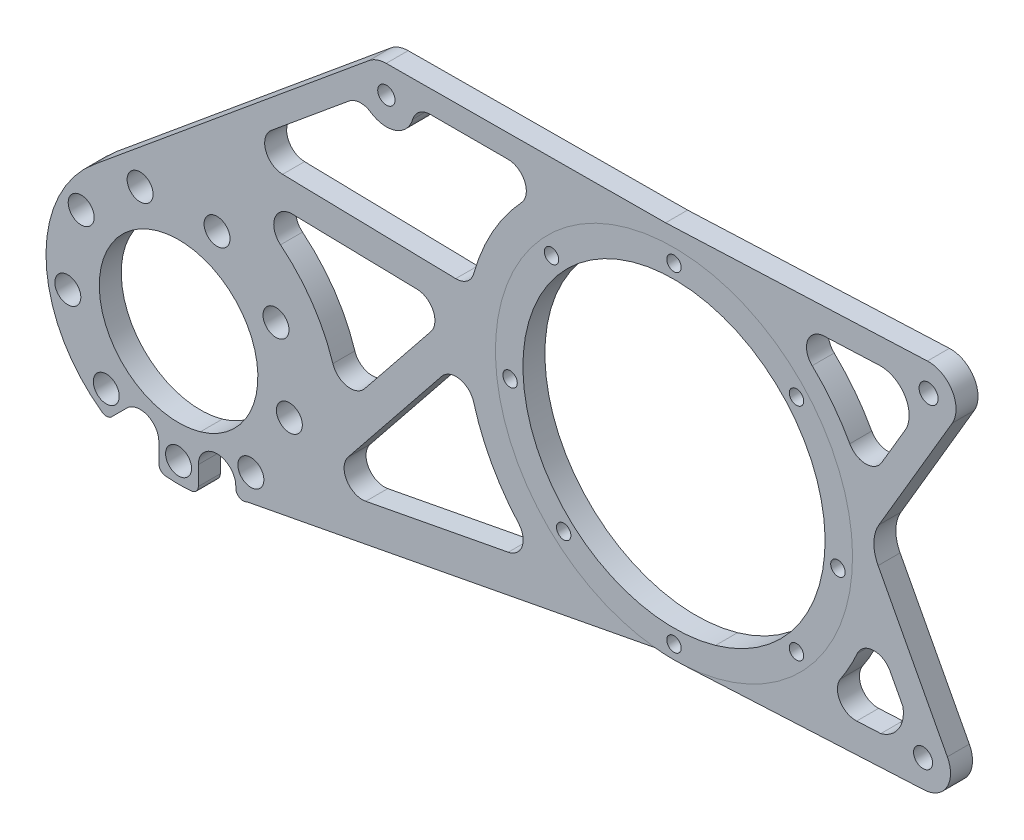
SolidWorks part; units mm, degrees
note: '?' marks a value the reader was unsure of.
material "6061-T6 (SS)"
ref_plane "X-Y Datum" through (0, 0, 0) normal (0, 0, 1) x (1, 0, 0)
ref_plane "X-Z Datum" through (0, 0, 0) normal (0, 1, 0) x (1, 0, 0)
ref_plane "Y-Z Datum" through (0, 0, 0) normal (1, 0, 0) x (0, 0, -1)
sketch "Sketch15" plane through (0, 0, 0) normal (0, 0, 1) x (-1, 0, 0)
  line L0 (-666.75, 77.9015) -> (-548.64, 0) construction
  line L1 (-666.75, 77.9015) -> (-494.9785, 127) construction
  line L8 (-471.7786, 164.3167) -> (-477.0435, 159.0518)
  line L9 (-488.1397, 163.648) -> (-488.1397, 170.2207)
  line L10 (-501.8173, 170.2207) -> (-501.8173, 163.648)
  line L11 (-514.8173, 163.648) -> (-514.8173, 164.225)
  line L17 (-660.4, 0) -> (-548.64, 0)
  line L18 (-777.24, 0) -> (-660.4, 0)
  line L19 (-777.24, 145.034) -> (-777.24, 0)
  line L20 (-789.94, 132.334) -> (-764.54, 157.734)
  line L21 (-789.94, 157.734) -> (-764.54, 132.334)
  line L22 (-789.94, 132.334) -> (-764.54, 132.334)
  line L23 (-789.94, 157.734) -> (-764.54, 157.734)
  line L24 (-789.94, 157.734) -> (-789.94, 132.334)
  line L25 (-764.54, 157.734) -> (-764.54, 132.334)
  line L26 (-543.2372, -4.4272) -> (-459.4185, 97.8608)
  line L27 (-777.24, -6.985) -> (-548.64, -6.985)
  line L28 (-784.225, 0) -> (-784.225, 145.034)
  line L29 (-776.4928, 151.9789) -> (-660.1268, 139.4587)
  line L30 (-660.1268, 139.4587) -> (-518.666, 166.4019)
  circle A0 centre (-567.0211, 20.1088) radius 3 construction
  circle A1 centre (-666.75, 77.9015) radius 52.3875
  circle A2 centre (-777.24, 0) radius 12.7 construction
  circle A4 centre (-548.64, 0) radius 12.7
  circle A6 centre (-777.24, 0) radius 12.7
  circle A7 centre (-753.11, 125.984) radius 3.3 construction
  circle A8 centre (-755.0278, 15.6608) radius 3.3 construction
  circle A9 centre (-567.0211, 20.1088) radius 3 construction
  circle A10 centre (-753.11, 125.984) radius 3.3 construction
  circle A11 centre (-755.0278, 15.6608) radius 3.3 construction
  circle A12 centre (-777.24, 145.034) radius 12.7 construction
  arc A16 (-518.666, 166.4019) -> (-468.5208, 164.5979) centre (-494.9785, 127) ccw
  arc A17 (-468.5208, 164.5979) -> (-471.7786, 164.3167) centre (-469.9826, 162.5207) ccw
  arc A18 (-488.1397, 163.648) -> (-477.0435, 159.0518) centre (-481.6397, 163.648) ccw
  arc A19 (-488.1397, 170.2207) -> (-490.4283, 172.7483) centre (-490.6797, 170.2207) ccw
  arc A20 (-490.4283, 172.7483) -> (-499.5287, 172.7483) centre (-494.9785, 127) ccw
  arc A21 (-499.5287, 172.7483) -> (-501.8173, 170.2207) centre (-499.2773, 170.2207) ccw
  arc A22 (-514.8173, 163.648) -> (-501.8173, 163.648) centre (-508.3173, 163.648) ccw
  arc A23 (-514.8173, 164.225) -> (-518.666, 166.4019) centre (-517.3573, 164.225) ccw
  circle A30 centre (-709.2207, 116.1423) radius 2.5
  circle A31 centre (-624.2793, 39.6607) radius 2.5
  circle A33 centre (-709.2207, 39.6607) radius 2.5
  circle A34 centre (-723.5869, 83.8753) radius 2.5
  circle A35 centre (-609.9131, 83.8753) radius 2.5
  circle A36 centre (-666.75, 20.7515) radius 2.5
  arc A40 (-666.75, 132.5515) -> (-666.75, 137.5515) centre (-666.75, 135.0515) ccw
  arc A41 (-666.75, 137.5515) -> (-666.75, 132.5515) centre (-666.75, 135.0515) ccw
  circle A43 centre (-628.5092, 120.3722) radius 2.5
  circle A45 centre (-666.75, 77.9015) radius 61.9125
  circle A46 centre (-548.64, 0) radius 3.3
  circle A47 centre (-777.24, 0) radius 3.3
  circle A48 centre (-777.24, 145.034) radius 3.3
  circle A49 centre (-548.64, 0) radius 6.985
  circle A50 centre (-777.24, 0) radius 6.985
  circle A51 centre (-777.24, 145.034) radius 6.985
  circle A61 centre (-461.2035, 107.5) radius 4.5
  circle A62 centre (-481.6397, 90.352) radius 4.5
  circle A63 centre (-508.3173, 90.352) radius 4.5
  circle A64 centre (-528.7535, 107.5) radius 4.5
  circle A65 centre (-533.386, 133.7723) radius 4.5
  circle A66 centre (-520.0472, 156.8757) radius 4.5
  circle A67 centre (-494.9785, 166) radius 4.5
  circle A68 centre (-469.9098, 156.8757) radius 4.5
  circle A69 centre (-456.571, 133.7723) radius 4.5
  circle A71 centre (-494.9785, 127) radius 27.4955
  dimension "D2" = 6.6
  dimension "D3" = 6.6
  dimension "D4" = 6.6
  dimension "D5" = 13.97
  dimension "D6" = 13.97
  dimension "D7" = 13.97
  dimension "D1" = 141.4871
extrude "Boss-Extrude1" add sketch "Sketch15" along normal blind 7.62
ref_point "Point1"
ref_point "Point2"
ref_plane "Plane1" through (666.75, -77.9015, 0) normal (-0.9615, -0.2748, 0) x (0, 0, 1)
ref_plane "Plane2" through (494.9785, -127, 0) normal (0.9615, 0.2748, 0) x (0, 0, -1)
split line "Split Line1"
split line "Split Line2"
sketch "Sketch17" plane through (0, 0, 7.62) normal (0, 0, 1) x (1, 0, 0)
  circle A0 centre (666.75, -77.9015) radius 61.9125 construction
  circle A1 centre (666.75, -77.9015) radius 61.9125
split line "Split Line3"
ref_axis "Axis4" through (666.75, -77.9015, 7.62) along (0, 0, -1)?
ref_axis "Axis5" through (494.9785, -127, 7.62) along (0, 0, -1)?
sketch "Sketch18" plane through (0, 0, 7.62) normal (0, 0, 1) x (1, 0, 0)
  line L0 (734.2162, -69.8493) -> (666.75, -77.9015) construction
  line L1 (666.75, -77.9015) -> (753.11, -125.984) construction
  line L2 (663.8529, -10.0183) -> (566.9655, -10.584)
  line L3 (560.9502, -12.7692) -> (465.6763, -91.5741)
  line L4 (514.8173, -163.648) -> (514.8173, -164.225)
  line L5 (501.8173, -170.2207) -> (501.8173, -163.648)
  line L6 (488.1397, -163.648) -> (488.1397, -170.2207)
  line L7 (471.7786, -164.3167) -> (477.0435, -159.0518)
  line L8 (514.8173, -163.648) -> (514.8173, -164.225)
  line L9 (501.8173, -170.2207) -> (501.8173, -163.648)
  line L10 (488.1397, -163.648) -> (488.1397, -170.2207)
  line L11 (471.7786, -164.3167) -> (477.0435, -159.0518)
  line L12 (734.2162, -69.8493) -> (763.2387, -20.4886)
  line L13 (734.2162, -69.8493) -> (761.5313, -121.5334)
  line L14 (754.6217, -6.1445) -> (663.8529, -10.0183)
  line L16 (753.5916, -135.4968) -> (669.8804, -139.7348)
  line L20 (660.1268, -139.4587) -> (518.666, -166.4019) construction
  line L21 (660.1268, -139.4587) -> (518.666, -166.4019)
  circle A0 centre (666.75, -77.9015) radius 67.945 construction
  circle A1 centre (666.75, -77.9015) radius 52.3875
  circle A2 centre (666.75, -77.9015) radius 52.3875
  arc A3 (761.5313, -121.5334) -> (753.5916, -135.4968) centre (753.11, -125.984) cw
  arc A5 (754.6217, -6.1445) -> (763.2387, -20.4886) centre (755.0278, -15.6608) cw
  circle A7 centre (666.75, -77.9015) radius 61.9125 construction
  arc A8 (566.9655, -10.584) -> (560.9502, -12.7692) centre (567.0211, -20.1088) ccw
  arc A9 (669.8804, -139.7348) -> (660.1268, -139.4587) centre (666.75, -77.9015) cw
  arc A10 (514.8173, -164.225) -> (518.666, -166.4019) centre (517.3573, -164.225) ccw
  arc A11 (514.8173, -163.648) -> (501.8173, -163.648) centre (508.3173, -163.648) ccw
  arc A12 (499.5287, -172.7483) -> (501.8173, -170.2207) centre (499.2773, -170.2207) ccw
  arc A13 (490.4283, -172.7483) -> (499.5287, -172.7483) centre (494.9785, -127) ccw
  arc A14 (488.1397, -170.2207) -> (490.4283, -172.7483) centre (490.6797, -170.2207) ccw
  arc A15 (488.1397, -163.648) -> (477.0435, -159.0518) centre (481.6397, -163.648) ccw
  arc A16 (468.5208, -164.5979) -> (471.7786, -164.3167) centre (469.9826, -162.5207) ccw
  arc A17 (518.666, -166.4019) -> (468.5208, -164.5979) centre (494.9785, -127) ccw
  arc A18 (514.8173, -164.225) -> (518.666, -166.4019) centre (517.3573, -164.225) ccw
  arc A19 (514.8173, -163.648) -> (501.8173, -163.648) centre (508.3173, -163.648) ccw
  arc A20 (499.5287, -172.7483) -> (501.8173, -170.2207) centre (499.2773, -170.2207) ccw
  arc A21 (490.4283, -172.7483) -> (499.5287, -172.7483) centre (494.9785, -127) ccw
  arc A22 (488.1397, -170.2207) -> (490.4283, -172.7483) centre (490.6797, -170.2207) ccw
  arc A23 (488.1397, -163.648) -> (477.0435, -159.0518) centre (481.6397, -163.648) ccw
  arc A24 (468.5208, -164.5979) -> (471.7786, -164.3167) centre (469.9826, -162.5207) ccw
  arc A25 (518.666, -166.4019) -> (468.5208, -164.5979) centre (494.9785, -127) ccw
  circle A29 centre (567.0211, -20.1088) radius 3 construction
  circle A30 centre (753.11, -125.984) radius 3.3 construction
  circle A31 centre (755.0278, -15.6608) radius 3.3 construction
  circle A32 centre (567.0211, -20.1088) radius 3
  circle A33 centre (753.11, -125.984) radius 3.3
  circle A34 centre (755.0278, -15.6608) radius 3.3
  circle A35 centre (753.11, -125.984) radius 9.525 construction
  circle A36 centre (755.0278, -15.6608) radius 9.525 construction
  circle A37 centre (567.0211, -20.1088) radius 9.525 construction
  dimension "D5" = 135.89
  dimension "D6" = 19.05
  dimension "D7" = 35.914
  dimension "D1" = 0
  dimension "D2" = 0
extrude "Profile" cut sketch "Sketch18" against normal through all
fillet "Prof Fillet" radius 12.7 1 edges at (734.2162, -69.8493, 3.81)
sketch "Sketch19" plane through (0, 0, 7.62) normal (0, 0, 1) x (1, 0, 0)
  line L0 (732.4887, -55.2476) -> (756.1667, -14.9766) construction
  line L1 (756.1667, -14.9766) -> (700.9038, -17.3351) construction
  line L2 (754.6217, -6.1445) -> (663.8529, -10.0183) construction
  line L3 (737.8071, -63.7419) -> (763.2387, -20.4886) construction
  line L4 (514.8173, -163.648) -> (514.8173, -164.225)
  line L5 (501.8173, -170.2207) -> (501.8173, -163.648)
  line L6 (488.1397, -163.648) -> (488.1397, -170.2207)
  line L7 (471.7786, -164.3167) -> (477.0435, -159.0518)
  line L8 (514.8173, -163.648) -> (514.8173, -164.225)
  line L9 (501.8173, -170.2207) -> (501.8173, -163.648)
  line L10 (488.1397, -163.648) -> (488.1397, -170.2207)
  line L11 (471.7786, -164.3167) -> (477.0435, -159.0518)
  line L12 (734.7219, -92.5501) -> (752.0832, -125.4002) construction
  line L13 (752.0832, -125.4002) -> (715.7448, -127.2398) construction
  line L14 (737.5266, -76.1131) -> (761.5313, -121.5334) construction
  line L15 (746.1204, -114.1176) -> (734.7219, -92.5501)
  line L16 (738.4628, -126.0897) -> (715.7448, -127.2398)
  line L17 (732.4887, -55.2476) -> (747.1519, -30.3088)
  line L18 (753.5916, -135.4968) -> (669.8804, -139.7348) construction
  line L19 (737.5266, -76.1131) -> (761.5313, -121.5334) construction
  line L20 (737.9147, -15.7556) -> (700.9038, -17.3351)
  arc A0 (700.9038, -17.3351) -> (732.4887, -55.2476) centre (666.75, -77.9015) cw construction
  circle A1 centre (666.75, -77.9015) radius 52.3875
  circle A2 centre (666.75, -77.9015) radius 52.3875
  circle A3 centre (548.64, 0) radius 12.7
  circle A4 centre (548.64, 0) radius 12.7
  arc A5 (715.7448, -127.2398) -> (734.7219, -92.5501) centre (666.75, -77.9015) ccw
  circle A7 centre (666.75, -77.9015) radius 61.9125 construction
  arc A8 (715.7448, -127.2398) -> (734.7219, -92.5501) centre (666.75, -77.9015) ccw construction
  arc A10 (514.8173, -164.225) -> (518.666, -166.4019) centre (517.3573, -164.225) ccw
  arc A11 (514.8173, -163.648) -> (501.8173, -163.648) centre (508.3173, -163.648) ccw
  arc A12 (499.5287, -172.7483) -> (501.8173, -170.2207) centre (499.2773, -170.2207) ccw
  arc A13 (490.4283, -172.7483) -> (499.5287, -172.7483) centre (494.9785, -127) ccw
  arc A14 (488.1397, -170.2207) -> (490.4283, -172.7483) centre (490.6797, -170.2207) ccw
  arc A15 (488.1397, -163.648) -> (477.0435, -159.0518) centre (481.6397, -163.648) ccw
  arc A16 (468.5208, -164.5979) -> (471.7786, -164.3167) centre (469.9826, -162.5207) ccw
  arc A17 (518.666, -166.4019) -> (468.5208, -164.5979) centre (494.9785, -127) ccw
  arc A18 (514.8173, -164.225) -> (518.666, -166.4019) centre (517.3573, -164.225) ccw
  arc A19 (514.8173, -163.648) -> (501.8173, -163.648) centre (508.3173, -163.648) ccw
  arc A20 (499.5287, -172.7483) -> (501.8173, -170.2207) centre (499.2773, -170.2207) ccw
  arc A21 (490.4283, -172.7483) -> (499.5287, -172.7483) centre (494.9785, -127) ccw
  arc A22 (488.1397, -170.2207) -> (490.4283, -172.7483) centre (490.6797, -170.2207) ccw
  arc A23 (488.1397, -163.648) -> (477.0435, -159.0518) centre (481.6397, -163.648) ccw
  arc A24 (468.5208, -164.5979) -> (471.7786, -164.3167) centre (469.9826, -162.5207) ccw
  arc A25 (518.666, -166.4019) -> (468.5208, -164.5979) centre (494.9785, -127) ccw
  circle A26 centre (753.11, -125.984) radius 3.3 construction
  circle A27 centre (753.11, -125.984) radius 3.3 construction
  circle A28 centre (753.11, -125.984) radius 9.525 construction
  arc A29 (746.1204, -114.1176) -> (738.4628, -126.0897) centre (735.8004, -115.9518) cw
  circle A30 centre (755.0278, -15.6608) radius 3.3 construction
  circle A31 centre (755.0278, -15.6608) radius 3.3 construction
  circle A32 centre (755.0278, -15.6608) radius 9.525 construction
  arc A33 (737.9147, -15.7556) -> (747.1519, -30.3088) centre (738.3388, -25.6945) cw
  arc A34 (732.4887, -55.2476) -> (700.9038, -17.3351) centre (666.75, -77.9015) ccw
  dimension "D7" = 7.62
  dimension "D8" = 7.62
  dimension "D10" = 19.05
  dimension "D11" = 10.4817
  dimension "D13" = 19.05
  dimension "D14" = 16.689
  dimension "D5" = 8.89
  dimension "D6" = 8.89
  dimension "D9" = 10.16
  dimension "D4" = 10.16
  dimension "D12" = 17.3096
  dimension "D1" = 0
  dimension "D2" = 0
  dimension "D3" = 0
extrude "Cut-Extrude2" cut sketch "Sketch19" against normal through all
fillet "Fillet2" radius 6.35 4 edges at (700.9038, -17.3351, 3.81) (732.4887, -55.2476, 3.81) (734.7219, -92.5501, 3.81) (715.7448, -127.2398, 3.81)
sketch "Sketch22" plane through (0, 0, 7.62) normal (0, 0, 1) x (1, 0, 0)
  line L3 (663.8529, -10.0183) -> (566.9655, -10.584) construction
  line L4 (514.8173, -163.648) -> (514.8173, -164.225)
  line L5 (501.8173, -170.2207) -> (501.8173, -163.648)
  line L6 (488.1397, -163.648) -> (488.1397, -170.2207)
  line L7 (471.7786, -164.3167) -> (477.0435, -159.0518)
  line L8 (514.8173, -163.648) -> (514.8173, -164.225)
  line L9 (501.8173, -170.2207) -> (501.8173, -163.648)
  line L10 (488.1397, -163.648) -> (488.1397, -170.2207)
  line L11 (471.7786, -164.3167) -> (477.0435, -159.0518)
  line L12 (621.3887, -133.9086) -> (542.9827, -148.8422)
  line L13 (542.9827, -148.8422) -> (594.9409, -84.0572)
  line L14 (660.1268, -139.4587) -> (518.666, -166.4019) construction
  line L16 (576.3681, -18.2758) -> (626.2627, -18.2758)
  line L17 (596.1732, -63.2945) -> (513.9914, -61.4996)
  line L19 (502.834, -71.4184) -> (590.5176, -73.3334)
  line L20 (590.5176, -73.3334) -> (550.9456, -122.6744)
  line L22 (513.9914, -61.4996) -> (558.6156, -24.5891)
  line L23 (560.9502, -12.7692) -> (465.6763, -91.5741) construction
  arc A0 (594.9409, -84.0572) -> (621.3887, -133.9086) centre (666.75, -77.9015) ccw
  circle A1 centre (666.75, -77.9015) radius 52.3875
  circle A2 centre (666.75, -77.9015) radius 52.3875
  circle A3 centre (548.64, 0) radius 12.7
  circle A4 centre (548.64, 0) radius 12.7
  circle A5 centre (567.0211, -20.1088) radius 3 construction
  circle A7 centre (567.0211, -20.1088) radius 3 construction
  arc A8 (626.2627, -18.2758) -> (596.1732, -63.2945) centre (666.75, -77.9015) ccw
  arc A9 (502.834, -71.4184) -> (550.9456, -122.6744) centre (494.9785, -127) cw
  arc A10 (514.8173, -164.225) -> (518.666, -166.4019) centre (517.3573, -164.225) ccw
  arc A11 (514.8173, -163.648) -> (501.8173, -163.648) centre (508.3173, -163.648) ccw
  arc A12 (499.5287, -172.7483) -> (501.8173, -170.2207) centre (499.2773, -170.2207) ccw
  arc A13 (490.4283, -172.7483) -> (499.5287, -172.7483) centre (494.9785, -127) ccw
  arc A14 (488.1397, -170.2207) -> (490.4283, -172.7483) centre (490.6797, -170.2207) ccw
  arc A15 (488.1397, -163.648) -> (477.0435, -159.0518) centre (481.6397, -163.648) ccw
  arc A16 (468.5208, -164.5979) -> (471.7786, -164.3167) centre (469.9826, -162.5207) ccw
  arc A17 (518.666, -166.4019) -> (468.5208, -164.5979) centre (494.9785, -127) ccw
  arc A18 (514.8173, -164.225) -> (518.666, -166.4019) centre (517.3573, -164.225) ccw
  arc A19 (514.8173, -163.648) -> (501.8173, -163.648) centre (508.3173, -163.648) ccw
  arc A20 (499.5287, -172.7483) -> (501.8173, -170.2207) centre (499.2773, -170.2207) ccw
  arc A21 (490.4283, -172.7483) -> (499.5287, -172.7483) centre (494.9785, -127) ccw
  arc A22 (488.1397, -170.2207) -> (490.4283, -172.7483) centre (490.6797, -170.2207) ccw
  arc A23 (488.1397, -163.648) -> (477.0435, -159.0518) centre (481.6397, -163.648) ccw
  arc A24 (468.5208, -164.5979) -> (471.7786, -164.3167) centre (469.9826, -162.5207) ccw
  arc A25 (518.666, -166.4019) -> (468.5208, -164.5979) centre (494.9785, -127) ccw
  arc A26 (669.8804, -139.7348) -> (660.1268, -139.4587) centre (666.75, -77.9015) ccw construction
  circle A27 centre (567.0211, -20.1088) radius 9.525 construction
  arc A28 (576.3681, -18.2758) -> (558.6156, -24.5891) centre (567.0211, -20.1088) cw
  dimension "D6" = 10.16
  dimension "D7" = 10.16
  dimension "D14" = 10.16
  dimension "D4" = 19.05
  dimension "D5" = 12.7
  dimension "D8" = 55.7399
  dimension "D9" = 7.7466
  dimension "D10" = 7.62
  dimension "D12" = 51.9581
  dimension "D13" = 64.7849
  dimension "D15" = 10.16
  dimension "D16" = 10.16
  dimension "D17" = 1.7949
  dimension "D1" = 0
  dimension "D2" = 0
  dimension "D3" = 0
extrude "Cut-Extrude4" cut sketch "Sketch22" against normal through all
fillet "Fillet5" radius 6.35 11 edges at (621.3887, -133.9086, 3.81) (542.9827, -148.8422, 3.81) (594.9409, -84.0572, 3.81) (550.9456, -122.6744, 3.81) (590.5176, -73.3334, 3.81) (502.834, -71.4184, 3.81) (596.1732, -63.2945, 3.81) (626.2627, -18.2758, 3.81) (513.9914, -61.4996, 3.81) (558.6156, -24.5891, 3.81) (576.3681, -18.2758, 3.81)
